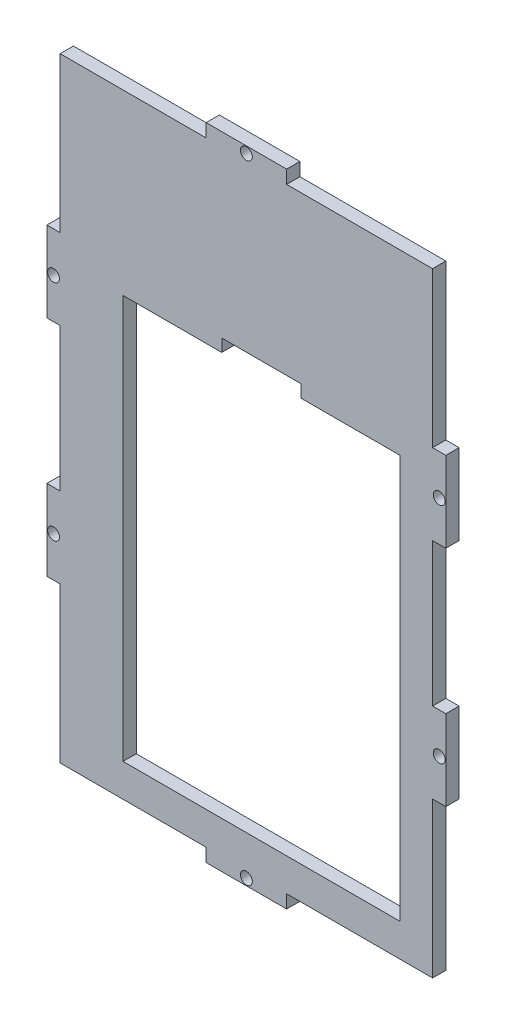
SolidWorks part; units mm, degrees
ref_plane "Front Plane" through (0, 0, 0) normal (0, 0, 1) x (1, 0, 0)
ref_plane "Top Plane" through (0, 0, 0) normal (0, 1, 0) x (1, 0, 0)
ref_plane "Right Plane" through (0, 0, 0) normal (1, 0, 0) x (0, 0, -1)
sketch "Sketch1" plane through (0, 0, 0) normal (0, 0, 1) x (1, 0, 0)
  line L0 (-44.645, 73.645) -> (-14.8817, 73.645)
  line L1 (-44.645, -73.645) -> (44.645, -73.645)
  line L2 (-44.645, -73.645) -> (-44.645, 73.645)
  line L3 (-44.645, 73.645) -> (44.645, 73.645) construction
  line L4 (44.645, -73.645) -> (44.645, 73.645)
  line L5 (-44.645, -73.645) -> (44.645, 73.645) construction
  line L6 (-44.645, 73.645) -> (44.645, -73.645) construction
  line L7 (-14.8817, 73.645) -> (14.8817, 73.645)
  line L8 (14.8817, 73.645) -> (44.645, 73.645)
  point P0 (0, 0)
  dimension "D1" = 89.29
  dimension "D2" = 147.29
extrude "Boss-Extrude1" add sketch "Sketch1" along normal blind 3.18
sketch "Sketch3" plane through (0, 0, 0) normal (0, 0, -1) x (-1, 0, 0)
  line L0 (-36.7767, 30.9733) -> (-36.7767, -65.7767)
  line L1 (-36.7767, -65.7767) -> (29.5733, -65.7767)
  line L2 (29.5733, -65.7767) -> (29.5733, 30.9733)
  line L3 (29.5733, 30.9733) -> (5.8983, 30.9733)
  line L4 (5.8983, 30.9733) -> (5.8983, 33.9733)
  line L5 (5.8983, 33.9733) -> (-13.1017, 33.9733)
  line L6 (-13.1017, 33.9733) -> (-13.1017, 30.9733)
  line L7 (-13.1017, 30.9733) -> (-36.7767, 30.9733)
  line L8 (29.5733, 39.9733) -> (-36.7767, 39.9733)
  line L9 (29.5733, -65.7767) -> (29.5733, 39.9733)
  line L10 (-36.7767, -65.7767) -> (29.5733, -65.7767)
  line L11 (-36.7767, 39.9733) -> (-36.7767, -65.7767)
  line L12 (-36.7767, -65.7767) -> (-36.7767, -73.645) construction
  line L13 (44.645, -73.645) -> (-44.645, -73.645) construction
  line L14 (-36.7767, -65.7767) -> (-44.645, -65.7767) construction
  line L15 (-44.645, -73.645) -> (-44.645, 73.645) construction
  dimension "D1" = 66.35
  dimension "D2" = 96.75
  dimension "D3" = 105.75
  dimension "D4" = 19
  dimension "D5" = 3
extrude "Cut-Extrude1" cut sketch "Sketch3" against normal through all contours L6 L7 L0 L1 L2 L3 L4 L5 region at (3.6017, -16.9628, 0)
sketch "Sketch9" plane through (-44.645, 0, 0) normal (-1, 0, 0) x (0, 0, 1)
  line L0 (0, 0) -> (3.18, 0) construction
  line L1 (0, 73.645) -> (0, -73.645) construction
  line L2 (3.18, 73.645) -> (3.18, -73.645) construction
  line L4 (0, -9.65) -> (3.18, -9.65)
  line L5 (0, -9.65) -> (0, 9.65)
  line L6 (0, 9.65) -> (3.18, 9.65)
  line L7 (3.18, -9.65) -> (3.18, 9.65)
  line L8 (0, -9.65) -> (3.18, 9.65) construction
  line L9 (0, 9.65) -> (3.18, -9.65) construction
  point P6 (1.59, 0)
  dimension "D1" = 19.3
extrude "Boss-Extrude4" [suppressed] add sketch "Sketch9" along normal blind 3.18
sketch "Sketch10" [suppressed] plane through (0, 0, 3.18) normal (0, 0, 1) x (1, 0, 0)
  line L0 (-46.235, 9.65) -> (-46.235, -9.65) construction
  line L1 (-47.825, 9.65) -> (-44.645, 9.65) construction
  line L2 (-47.825, -9.65) -> (-44.645, -9.65) construction
  circle A0 centre (-46.235, 0) radius 1.425
extrude "Cut-Extrude4" [suppressed] cut sketch "Sketch10" against normal through all
mirror "Mirror1" [suppressed] about plane through (0, 0, 0) normal (1, 0, 0)
sketch "Sketch18" plane through (44.645, 0, 0) normal (1, 0, 0) x (0, 0, -1)
  line L0 (0, 0) -> (-3.18, 0) construction
  line L1 (0, -73.645) -> (0, 73.645) construction
  line L2 (-3.18, -73.645) -> (-3.18, 73.645) construction
  line L4 (-3.18, -9.65) -> (0, -9.65)
  line L5 (-3.18, -9.65) -> (-3.18, 9.65)
  line L6 (-3.18, 9.65) -> (0, 9.65)
  line L7 (0, -9.65) -> (0, 9.65)
  line L8 (-3.18, -9.65) -> (0, 9.65) construction
  line L9 (-3.18, 9.65) -> (0, -9.65) construction
  point P6 (-1.59, 0)
  dimension "D1" = 19.3
extrude "Boss-Extrude8" [suppressed] add sketch "Sketch18" along normal blind 3.18
sketch "Sketch19" [suppressed] plane through (0, 0, 3.18) normal (0, 0, 1) x (1, 0, 0)
  line L0 (46.235, -9.65) -> (46.235, 9.65) construction
  line L1 (47.825, -9.65) -> (44.645, -9.65) construction
  line L2 (47.825, 9.65) -> (44.645, 9.65) construction
  circle A0 centre (46.235, 0) radius 1.425
extrude "Cut-Extrude8" [suppressed] cut sketch "Sketch19" against normal through all
mirror "Mirror2" [suppressed] about plane through (0, 0, 0) normal (1, 0, 0)
sketch "Sketch20" plane through (0, 0, 3.18) normal (0, 0, 1) x (1, 0, 0)
  line L0 (0, 70.465) -> (0, 0) construction
  line L1 (44.645, 73.645) -> (-44.645, 73.645) construction
  line L2 (-9.65, 73.645) -> (9.65, 73.645)
  line L3 (9.65, 73.645) -> (9.65, 70.465)
  line L4 (9.65, 70.465) -> (1.425, 70.465)
  line L5 (1.425, 70.465) -> (1.425, 62.665)
  line L6 (1.425, 62.665) -> (3.175, 62.665)
  line L7 (3.175, 62.665) -> (3.175, 60.285)
  line L8 (3.175, 60.285) -> (1.425, 60.285)
  line L9 (1.425, 60.285) -> (1.425, 54.665)
  line L10 (1.425, 54.665) -> (-1.425, 54.665)
  line L11 (-1.425, 54.665) -> (-1.425, 60.285)
  line L12 (-1.425, 60.285) -> (-3.175, 60.285)
  line L13 (-3.175, 60.285) -> (-3.175, 62.665)
  line L14 (-3.175, 62.665) -> (-1.425, 62.665)
  line L15 (-1.425, 62.665) -> (-1.425, 70.465)
  line L16 (-1.425, 70.465) -> (-9.65, 70.465)
  line L17 (-9.65, 70.465) -> (-9.65, 73.645)
  dimension "D1" = 19.3
  dimension "D2" = 3.18
  dimension "D3" = 15.8
  dimension "D4" = 6.35
  dimension "D5" = 2.38
  dimension "D6" = 2.85
  dimension "D7" = 7.8
extrude "Cut-Extrude9" [suppressed] cut sketch "Sketch20" against normal through all
mirror "Mirror3" [suppressed] about plane through (0, 0, 0) normal (0, 1, 0)
sketch "Sketch23" plane through (0, 0, 3.18) normal (0, 0, 1) x (1, 0, 0)
  line L0 (-44.645, 13.995) -> (-44.645, 33.295)
  line L1 (-44.645, 73.645) -> (-44.645, -73.645) construction
  line L2 (-44.645, 33.295) -> (-41.465, 33.295)
  line L3 (-41.465, 33.295) -> (-41.465, 25.07)
  line L4 (-41.465, 25.07) -> (-33.665, 25.07)
  line L5 (-33.665, 25.07) -> (-33.665, 26.82)
  line L6 (-33.665, 26.82) -> (-31.285, 26.82)
  line L7 (-31.285, 26.82) -> (-31.285, 25.07)
  line L8 (-31.285, 25.07) -> (-25.665, 25.07)
  line L9 (-25.665, 25.07) -> (-25.665, 22.22)
  line L10 (-25.665, 22.22) -> (-31.285, 22.22)
  line L11 (-31.285, 22.22) -> (-31.285, 20.47)
  line L12 (-31.285, 20.47) -> (-33.665, 20.47)
  line L13 (-33.665, 20.47) -> (-33.665, 22.22)
  line L14 (-33.665, 22.22) -> (-41.465, 22.22)
  line L15 (-41.465, 22.22) -> (-41.465, 13.995)
  line L16 (-41.465, 13.995) -> (-44.645, 13.995)
  line L17 (44.645, 73.645) -> (-44.645, 73.645) construction
  line L19 (-25.665, 23.645) -> (-44.645, 23.645) construction
  line L20 (-44.645, -33.295) -> (-44.645, -13.995)
  line L21 (-44.645, -13.995) -> (-41.465, -13.995)
  line L22 (-41.465, -13.995) -> (-41.465, -22.22)
  line L23 (-41.465, -22.22) -> (-33.665, -22.22)
  line L24 (-33.665, -22.22) -> (-33.665, -20.47)
  line L25 (-33.665, -20.47) -> (-31.285, -20.47)
  line L26 (-31.285, -20.47) -> (-31.285, -22.22)
  line L27 (-31.285, -22.22) -> (-25.665, -22.22)
  line L28 (-25.665, -22.22) -> (-25.665, -25.07)
  line L29 (-25.665, -25.07) -> (-31.285, -25.07)
  line L30 (-31.285, -25.07) -> (-31.285, -26.82)
  line L31 (-31.285, -26.82) -> (-33.665, -26.82)
  line L32 (-33.665, -26.82) -> (-33.665, -25.07)
  line L33 (-33.665, -25.07) -> (-41.465, -25.07)
  line L34 (-41.465, -25.07) -> (-41.465, -33.295)
  line L35 (-41.465, -33.295) -> (-44.645, -33.295)
  line L36 (-44.645, -23.645) -> (-25.665, -23.645) construction
  line L37 (-44.645, -73.645) -> (44.645, -73.645) construction
  dimension "D1" = 50
  dimension "D2" = 19.3
  dimension "D3" = 3.18
  dimension "D4" = 15.8
  dimension "D5" = 6.35
  dimension "D6" = 2.85
  dimension "D7" = 7.8
  dimension "D8" = 2.38
  dimension "D9" = 19.3
  dimension "D10" = 3.18
  dimension "D11" = 7.8
  dimension "D12" = 15.8
  dimension "D13" = 6.35
  dimension "D14" = 2.85
  dimension "D15" = 2.38
  dimension "D16" = 50
  dimension "D17" = 1.75
extrude "Cut-Extrude10" [suppressed] cut sketch "Sketch23" against normal through all
sketch "Sketch24" plane through (0, 0, 3.18) normal (0, 0, 1) x (1, 0, 0)
  line L0 (44.645, -13.995) -> (44.645, -33.295)
  line L1 (44.645, -73.645) -> (44.645, 73.645) construction
  line L2 (44.645, -33.295) -> (41.465, -33.295)
  line L3 (41.465, -33.295) -> (41.465, -25.07)
  line L4 (41.465, -25.07) -> (33.665, -25.07)
  line L5 (33.665, -25.07) -> (33.665, -26.82)
  line L6 (33.665, -26.82) -> (31.285, -26.82)
  line L7 (31.285, -26.82) -> (31.285, -25.07)
  line L8 (31.285, -25.07) -> (25.665, -25.07)
  line L9 (25.665, -25.07) -> (25.665, -22.22)
  line L10 (25.665, -22.22) -> (31.285, -22.22)
  line L11 (31.285, -22.22) -> (31.285, -20.47)
  line L12 (31.285, -20.47) -> (33.665, -20.47)
  line L13 (33.665, -20.47) -> (33.665, -22.22)
  line L14 (33.665, -22.22) -> (41.465, -22.22)
  line L15 (41.465, -22.22) -> (41.465, -13.995)
  line L16 (41.465, -13.995) -> (44.645, -13.995)
  line L17 (25.665, -23.645) -> (44.645, -23.645) construction
  line L18 (-44.645, -73.645) -> (44.645, -73.645) construction
  line L19 (44.645, 33.295) -> (44.645, 13.995)
  line L20 (44.645, 13.995) -> (41.465, 13.995)
  line L21 (41.465, 13.995) -> (41.465, 22.22)
  line L22 (41.465, 22.22) -> (33.665, 22.22)
  line L23 (33.665, 22.22) -> (33.665, 20.47)
  line L24 (33.665, 20.47) -> (31.285, 20.47)
  line L25 (31.285, 20.47) -> (31.285, 22.22)
  line L26 (31.285, 22.22) -> (25.665, 22.22)
  line L27 (25.665, 22.22) -> (25.665, 25.07)
  line L28 (25.665, 25.07) -> (31.285, 25.07)
  line L29 (31.285, 25.07) -> (31.285, 26.82)
  line L30 (31.285, 26.82) -> (33.665, 26.82)
  line L31 (33.665, 26.82) -> (33.665, 25.07)
  line L32 (33.665, 25.07) -> (41.465, 25.07)
  line L33 (41.465, 25.07) -> (41.465, 33.295)
  line L34 (41.465, 33.295) -> (44.645, 33.295)
  line L35 (25.665, 23.645) -> (44.645, 23.645) construction
  line L36 (44.645, 73.645) -> (-44.645, 73.645) construction
  dimension "D1" = 19.3
  dimension "D2" = 3.18
  dimension "D3" = 15.8
  dimension "D4" = 7.8
  dimension "D5" = 6.35
  dimension "D6" = 2.85
  dimension "D7" = 2.38
  dimension "D8" = 50
  dimension "D9" = 19.3
  dimension "D10" = 3.18
  dimension "D11" = 7.8
  dimension "D12" = 15.8
  dimension "D13" = 6.35
  dimension "D14" = 2.85
  dimension "D15" = 2.38
  dimension "D16" = 50
extrude "Cut-Extrude11" [suppressed] cut sketch "Sketch24" against normal through all
sketch "Sketch25" plane through (0, 0, 3.18) normal (0, 0, 1) x (1, 0, 0)
  line L0 (9.65, -73.645) -> (-9.65, -73.645)
  line L1 (-44.645, -73.645) -> (44.645, -73.645) construction
  line L2 (-9.65, -73.645) -> (-9.65, -70.465)
  line L3 (-9.65, -70.465) -> (-1.425, -70.465)
  line L4 (-1.425, -70.465) -> (-1.425, -62.665)
  line L5 (-1.425, -62.665) -> (-3.175, -62.665)
  line L6 (-3.175, -62.665) -> (-3.175, -60.285)
  line L7 (-3.175, -60.285) -> (-1.425, -60.285)
  line L8 (-1.425, -60.285) -> (-1.425, -54.665)
  line L9 (-1.425, -54.665) -> (1.425, -54.665)
  line L10 (1.425, -54.665) -> (1.425, -60.285)
  line L11 (1.425, -60.285) -> (3.175, -60.285)
  line L12 (3.175, -60.285) -> (3.175, -62.665)
  line L13 (3.175, -62.665) -> (1.425, -62.665)
  line L14 (1.425, -62.665) -> (1.425, -70.465)
  line L15 (1.425, -70.465) -> (9.65, -70.465)
  line L16 (9.65, -70.465) -> (9.65, -73.645)
  line L17 (0, -73.645) -> (0, 0) construction
  dimension "D1" = 19.3
  dimension "D2" = 3.18
  dimension "D3" = 15.8
  dimension "D4" = 7.8
  dimension "D5" = 6.35
  dimension "D6" = 2.85
  dimension "D7" = 2.38
extrude "Cut-Extrude12" [suppressed] cut sketch "Sketch25" against normal through all
sketch "Sketch26" plane through (0, 0, 3.18) normal (0, 0, 1) x (1, 0, 0)
  line L0 (-9.65, 73.645) -> (9.65, 73.645)
  line L1 (44.645, 73.645) -> (-44.645, 73.645) construction
  line L2 (9.65, 73.645) -> (9.65, 70.465)
  line L3 (9.65, 70.465) -> (1.425, 70.465)
  line L4 (1.425, 70.465) -> (1.425, 62.665)
  line L5 (1.425, 62.665) -> (3.175, 62.665)
  line L6 (3.175, 62.665) -> (3.175, 60.285)
  line L7 (3.175, 60.285) -> (1.425, 60.285)
  line L8 (1.425, 60.285) -> (1.425, 54.665)
  line L9 (1.425, 54.665) -> (-1.425, 54.665)
  line L10 (-1.425, 54.665) -> (-1.425, 60.285)
  line L11 (-1.425, 60.285) -> (-3.175, 60.285)
  line L12 (-3.175, 60.285) -> (-3.175, 62.665)
  line L13 (-3.175, 62.665) -> (-1.425, 62.665)
  line L14 (-1.425, 62.665) -> (-1.425, 70.465)
  line L15 (-1.425, 70.465) -> (-9.65, 70.465)
  line L16 (-9.65, 70.465) -> (-9.65, 73.645)
  line L17 (0, 73.645) -> (0, -4.4192) construction
  dimension "D1" = 19.3
  dimension "D2" = 3.18
  dimension "D3" = 7.8
  dimension "D4" = 15.8
  dimension "D5" = 6.35
  dimension "D6" = 2.85
  dimension "D7" = 2.38
extrude "Cut-Extrude13" [suppressed] cut sketch "Sketch26" against normal through all
mirror "Mirror4" [suppressed] about plane through (0, 0, 0) normal (1, 0, 0)
mirror "Mirror5" [suppressed] about plane through (0, 0, 0) normal (1, 0, 0)
mirror "Mirror6" [suppressed] about plane through (0, 0, 0) normal (0, 1, 0)
mirror "Mirror7" [suppressed] about plane through (0, 0, 0) normal (0, 1, 0)
sketch "Sketch27" plane through (-44.645, 0, 0) normal (-1, 0, 0) x (0, 0, 1)
  line L0 (0, -36.475) -> (0, -17.175)
  line L1 (0, 73.645) -> (0, -73.645) construction
  line L2 (0, -17.175) -> (3.18, -17.175)
  line L3 (3.18, 73.645) -> (3.18, -73.645) construction
  line L4 (3.18, -17.175) -> (3.18, -36.475)
  line L5 (3.18, -36.475) -> (0, -36.475)
  line L6 (3.18, -26.825) -> (0, -26.825) construction
  line L7 (3.18, -73.645) -> (0, -73.645) construction
  dimension "D1" = 19.3
  dimension "D2" = 46.82
extrude "Boss-Extrude9" add sketch "Sketch27" along normal blind 3.18
sketch "Sketch28" plane through (0, -73.645, 0) normal (0, -1, 0) x (1, 0, 0)
  line L0 (9.65, 0) -> (-9.65, 0)
  line L1 (-44.645, 0) -> (44.645, 0) construction
  line L2 (-9.65, 0) -> (-9.65, 3.18)
  line L3 (-44.645, 3.18) -> (44.645, 3.18) construction
  line L4 (-9.65, 3.18) -> (9.65, 3.18)
  line L5 (9.65, 3.18) -> (9.65, 0)
  line L6 (0, 0) -> (0, 3.18) construction
  dimension "D1" = 19.3
extrude "Boss-Extrude10" add sketch "Sketch28" along normal blind 3.18
sketch "Sketch29" plane through (0, 0, 3.18) normal (0, 0, 1) x (1, 0, 0)
  line L0 (-47.825, -26.825) -> (-37.3062, -26.825) construction
  line L1 (-47.825, -36.475) -> (-47.825, -17.175) construction
  line L2 (-46.235, -17.175) -> (-46.235, -36.475) construction
  line L3 (-47.825, -17.175) -> (-44.645, -17.175) construction
  line L4 (-47.825, -36.475) -> (-44.645, -36.475) construction
  circle A0 centre (-46.235, -26.825) radius 1.425
extrude "Cut-Extrude14" cut sketch "Sketch29" against normal through all
sketch "Sketch30" plane through (0, 0, 3.18) normal (0, 0, 1) x (1, 0, 0)
  line L0 (0, -76.825) -> (0, -66.2855) construction
  line L1 (9.65, -76.825) -> (-9.65, -76.825) construction
  line L2 (9.65, -75.235) -> (-9.65, -75.235) construction
  line L3 (9.65, -76.825) -> (9.65, -73.645) construction
  line L4 (-9.65, -76.825) -> (-9.65, -73.645) construction
  circle A0 centre (0, -75.235) radius 1.425
extrude "Cut-Extrude15" cut sketch "Sketch30" against normal through all
mirror "Mirror8" about plane through (0, 0, 0) normal (1, 0, 0) of "Cut-Extrude14", "Boss-Extrude9"
mirror "Mirror9" about plane through (0, 0, 0) normal (0, 1, 0) of "Cut-Extrude15", "Boss-Extrude10", "Mirror8"
